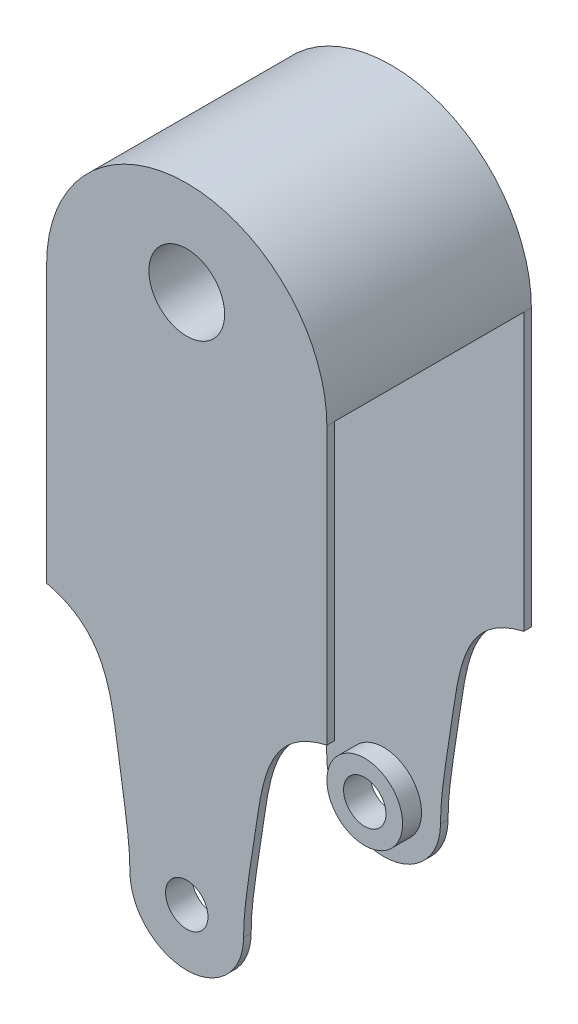
SolidWorks part; units mm, degrees
ref_plane "Alzado" through (0, 0, 0) normal (0, 0, 1) x (1, 0, 0)
ref_plane "Planta" through (0, 0, 0) normal (0, 1, 0) x (1, 0, 0)
ref_plane "Vista lateral" through (0, 0, 0) normal (1, 0, 0) x (0, 0, -1)
sketch "Croquis1" plane through (0, 0, 0) normal (0, 0, 1) x (1, 0, 0)
  line L2 (74, 180) -> (37, 180) construction
  line L3 (0, 143) -> (0, 70)
  line L4 (74, 143) -> (74, 180) construction
  line L6 (37, 0) -> (37, 15)
  line L7 (37, 15) -> (37, 40) construction
  line L8 (37, 40) -> (19, 40) construction
  line L9 (74, 143) -> (74, 70)
  line L10 (74, 70) -> (74, 0) construction
  line L11 (37, 180) -> (37, 155) construction
  arc A0 (74, 143) -> (0, 143) centre (37, 143) ccw
  circle A2 centre (37, 15) radius 5.6
  arc A3 (22, 15) -> (52, 15) centre (37, 15) ccw
  circle A4 centre (37, 155) radius 10
  spline S0 degree 3 poles (52, 15) (52, 22.318) (56.2223, 44.5245) (58.0965, 66.3006) (74, 70) knots 0 0 0 0 0.399675 1 1 1 1
  spline S1 degree 3 poles (22, 15) (22, 22.318) (17.7777, 44.5245) (15.9035, 66.3006) (0, 70) knots 0 0 0 0 0.399675 1 1 1 1
  dimension "D3" = 20
  dimension "D4" = 11.2
  dimension "D9" = 15
  dimension "D1" = 180
  dimension "D2" = 74
  dimension "D5" = 15
  dimension "D6" = 25
  dimension "D7" = 18
  dimension "D8" = 20
  dimension "D11" = 25
extrude "Saliente-Extruir1" add sketch "Croquis1" along normal blind 54 contours S1 A3 A2 S0 L9 A0 L3 A4 region at (37, 100.3084, 0)
sketch "Croquis2" plane through (74, 0, 0) normal (1, 0, 0) x (0, 0, -1)
  line L0 (-54, 70) -> (-52, 70) construction
  line L1 (-54, 70) -> (0, 70) construction
  line L2 (-52, 70) -> (-2, 70)
  line L3 (-2, 70) -> (0, 70) construction
  line L4 (-52, 70) -> (-52, 20.6)
  line L9 (-52, 20.6) -> (-49, 20.6)
  line L10 (-49, 20.6) -> (-49, 9.4)
  line L11 (-52, 9.4) -> (-49, 9.4)
  line L12 (-52, 9.4) -> (-52, 0)
  line L17 (-2, 9.4) -> (-2, 0)
  line L18 (-2, 9.4) -> (-5, 9.4)
  line L19 (-5, 20.6) -> (-5, 9.4)
  line L20 (-2, 20.6) -> (-5, 20.6)
  line L21 (-2, 70) -> (-2, 20.6)
  line L22 (0, 70) -> (-2, 70) construction
  line L27 (-52, 0) -> (-2, 0)
  point P9 (0, 0)
  point P16 (-49, 15)
  point P31 (-5, 15)
  point P32 (-50.5, 9.4)
  dimension "D1" = 11.2
  dimension "D4" = 3
sketch "Croquis6" plane through (0, 0, 0) normal (-1, 0, 0) x (0, 0, 1)
  line L0 (0, 70) -> (0, 0)
  line L1 (0, 0) -> (54, 0)
  line L2 (54, 0) -> (54, 70)
  line L3 (54, 70) -> (0, 70)
extrude "Saliente-Extruir3" add sketch "Croquis6" against normal blind 74
sketch "Croquis7" plane through (74, 0, 0) normal (1, 0, 0) x (0, 0, -1)
  line L0 (-52, 0) -> (-2, 0)
  line L1 (-2, 0) -> (-2, 9.4)
  line L2 (-2, 9.4) -> (-5, 9.4)
  line L3 (-5, 9.4) -> (-5, 20.6)
  line L4 (-5, 20.6) -> (-2, 20.6)
  line L5 (-2, 20.6) -> (-2, 70)
  line L6 (-2, 70) -> (-52, 70)
  line L7 (-52, 70) -> (-52, 20.6)
  line L8 (-52, 20.6) -> (-49, 20.6)
  line L9 (-49, 20.6) -> (-49, 9.4)
  line L10 (-49, 9.4) -> (-52, 9.4)
  line L11 (-52, 9.4) -> (-52, 0)
extrude "Cortar-Extruir13" cut sketch "Croquis7" against normal blind 74
sketch "Croquis8" plane through (0, 0, 0) normal (0, 0, -1) x (-1, 0, 0)
  line L0 (-74, 70) -> (-74, 0)
  line L1 (-74, 0) -> (-37, 0)
  line L2 (-37, 0) -> (0, 0)
  line L3 (0, 0) -> (0, 70)
  circle A0 centre (-37, 15) radius 5.6
  arc A1 (-52, 15) -> (-22, 15) centre (-37, 15) ccw
  spline S0 degree 3 poles (-74, 70) (-58.0965, 66.3006) (-56.2223, 44.5245) (-52, 22.318) (-52, 15) knots 0 0 0 0 0.600325 1 1 1 1
  spline S1 degree 3 poles (-22, 15) (-22, 22.318) (-17.7777, 44.5245) (-15.9035, 66.3006) (0, 70) knots 0 0 0 0 0.399675 1 1 1 1
  line M1 (-74, 0) -> (0, 0)
  line M2 (0, 0) -> (0, 143)
  line M4 (-74, 143) -> (-74, 0)
extrude "Cortar-Extruir14" cut sketch "Croquis8" against normal blind 74 contours S0 A1 M4 M1 | S1 A1 M1 M2 region at (63.7137, 29.7224, 0) region at (10.2863, 29.7224, 0)
sketch "Croquis9" plane through (74, 0, 0) normal (1, 0, 0) x (0, 0, -1)
  line L0 (-49, 20.6) -> (-52, 20.6)
  line L1 (-52, 20.6) -> (-52, 9.4)
  line L2 (-52, 9.4) -> (-49, 9.4)
  line L3 (-49, 9.4) -> (-49, 20.6)
  line L4 (-2, 20.6) -> (-5.1988, 20.6)
  line L5 (-5.1988, 20.6) -> (-5, 9.4)
  line L6 (-5, 9.4) -> (-2, 9.4)
  line L7 (-2, 20.6) -> (-2, 9.4)
extrude "Cortar-Extruir15" cut sketch "Croquis9" against normal blind 74
sketch "Croquis10" plane through (0, 0, 0) normal (0, 0, -1) x (-1, 0, 0)
  circle A0 centre (-37, 15) radius 5.6
extrude "Cortar-Extruir16" cut sketch "Croquis10" against normal blind 74
sketch "Croquis11" plane through (0, 0, 52) normal (0, 0, -1) x (-1, 0, 0)
  circle A0 centre (-37, 15) radius 10
  circle A1 centre (-37, 15) radius 5.6
  dimension "D1" = 20
extrude "Saliente-Extruir4" add sketch "Croquis11" along normal blind 5
sketch "Croquis12" plane through (0, 0, 2) normal (0, 0, 1) x (1, 0, 0)
  circle A0 centre (37, 15) radius 5.6
  circle A1 centre (37, 15) radius 10
  dimension "D1" = 20
extrude "Saliente-Extruir5" add sketch "Croquis12" along normal blind 5
sketch "Croquis13" plane through (0, 0, 0) normal (-1, 0, 0) x (0, 0, 1)
  line L0 (2, 70) -> (2, 143)
  line L1 (54, 143) -> (0, 143) construction
  line L2 (2, 143) -> (52, 143)
  line L3 (52, 143) -> (52, 70)
  line L4 (52, 70) -> (2, 70)
extrude "Cortar-Extruir17" cut sketch "Croquis13" against normal blind 74
